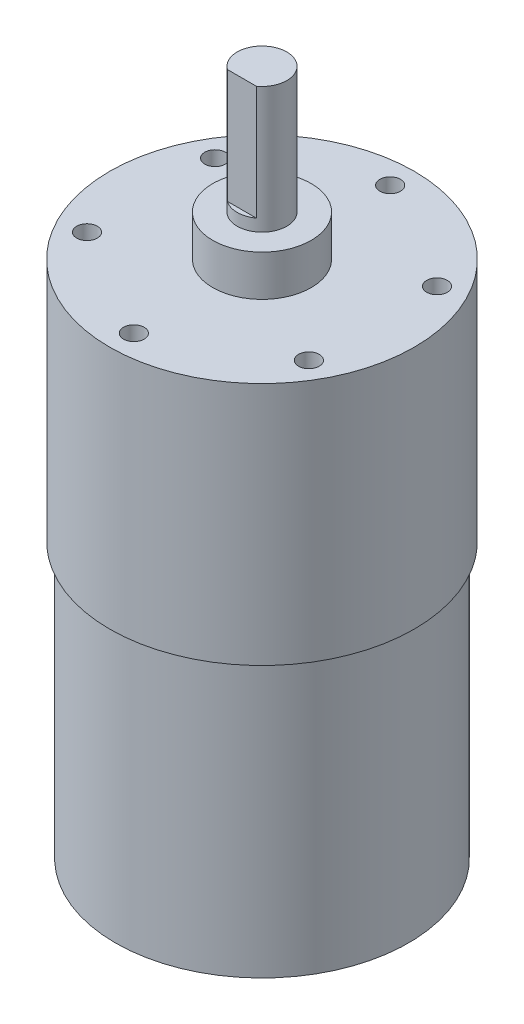
SolidWorks part; units mm, degrees
ref_plane "Front Plane" through (0, 0, 0) normal (0, 0, 1) x (1, 0, 0)
ref_plane "Top Plane" through (0, 0, 0) normal (0, 1, 0) x (1, 0, 0)
ref_plane "Right Plane" through (0, 0, 0) normal (1, 0, 0) x (0, 0, -1)
sketch "Sketch1" plane through (0, 0, 0) normal (0, 1, 0) x (1, 0, 0)
  circle A0 centre (0, 0) radius 18.4277
  dimension "D1" = 36.8554
extrude "Boss-Extrude1" add sketch "Sketch1" along normal blind 29.5402
sketch "Sketch2" plane through (0, 29.5402, 0) normal (0, 1, 0) x (1, 0, 0)
  circle A0 centre (0, 0) radius 5.9563
  dimension "D1" = 11.9126
extrude "Boss-Extrude2" add sketch "Sketch2" along normal blind 4.953
sketch "Sketch3" plane through (0, 34.4932, 0) normal (0, 1, 0) x (1, 0, 0)
  circle A0 centre (0, 0) radius 3
  dimension "D1" = 6
extrude "Boss-Extrude3" add sketch "Sketch3" along normal blind 15.2654
sketch "Sketch4" plane through (0, 49.7586, 0) normal (0, 1, 0) x (1, 0, 0)
  line L0 (-1.7516, -2.4356) -> (1.7516, -2.4356)
  arc A0 (-1.7516, -2.4356) -> (1.7516, -2.4356) centre (0, 0) ccw
  dimension "D1" = 5.4356
extrude "Cut-Extrude1" cut sketch "Sketch4" against normal blind 13.8176
sketch "Sketch5" plane through (0, 0, 0) normal (0, -1, 0) x (1, 0, 0)
  circle A0 centre (0, 0) radius 17.7419
  dimension "D1" = 35.4838
extrude "Boss-Extrude4" add sketch "Sketch5" along normal blind 33.2232
sketch "Sketch6" plane through (0, -33.2232, 0) normal (0, -1, 0) x (-1, 0, 0)
  circle A0 centre (0, 0) radius 5.0292
  dimension "D1" = 10.0584
extrude "Boss-Extrude5" add sketch "Sketch6" along normal blind 3.048
chamfer "Chamfer1" distance 1.5875 angle 45 1 edges at (0, -36.2712, -5.0292)
hole_wizard "Tap Drill for M3x0.5 Tap1" positions "Sketch7" profile "Sketch9" hole size "M3x0.5" standard "ANSI Metric"
sketch "Sketch7" plane through (0, 29.5402, 0) normal (0, 1, 0) x (1, 0, 0)
  line L0 (0, 0) -> (0, 15.5) construction
  point P0 (0, 15.5)
  point P25 (13.4234, 7.75)
  point P26 (13.4234, -7.75)
  point P27 (0, -15.5)
  point P28 (-13.4234, -7.75)
  point P29 (-13.4234, 7.75)
  point P30 (0, 0)
  point P31 (0, 0)
  point P32 (0, 0)
  dimension "D1" = 15.5
  dimension "D2" = 6
sketch "Sketch9" plane through (0, 29.5402, -15.5) normal (1, 0, 0) x (0, 0, 1)
  line L0 (0, 0) -> (0, 5.8311)
  line L1 (0, 5.8311) -> (1.25, 5.08)
  line L2 (1.25, 5.08) -> (1.25, 0)
  line L5 (1.25, 0) -> (0, 0)
  line L10 (0, 5.8311) -> (-1.25, 5.08) construction
  line L11 (0, -6.35) -> (0, 107.95) construction
  dimension "Hole Dia." = 2.5
  dimension "Hole Depth" = 5.08
  dimension "Drill Angle" = 118
